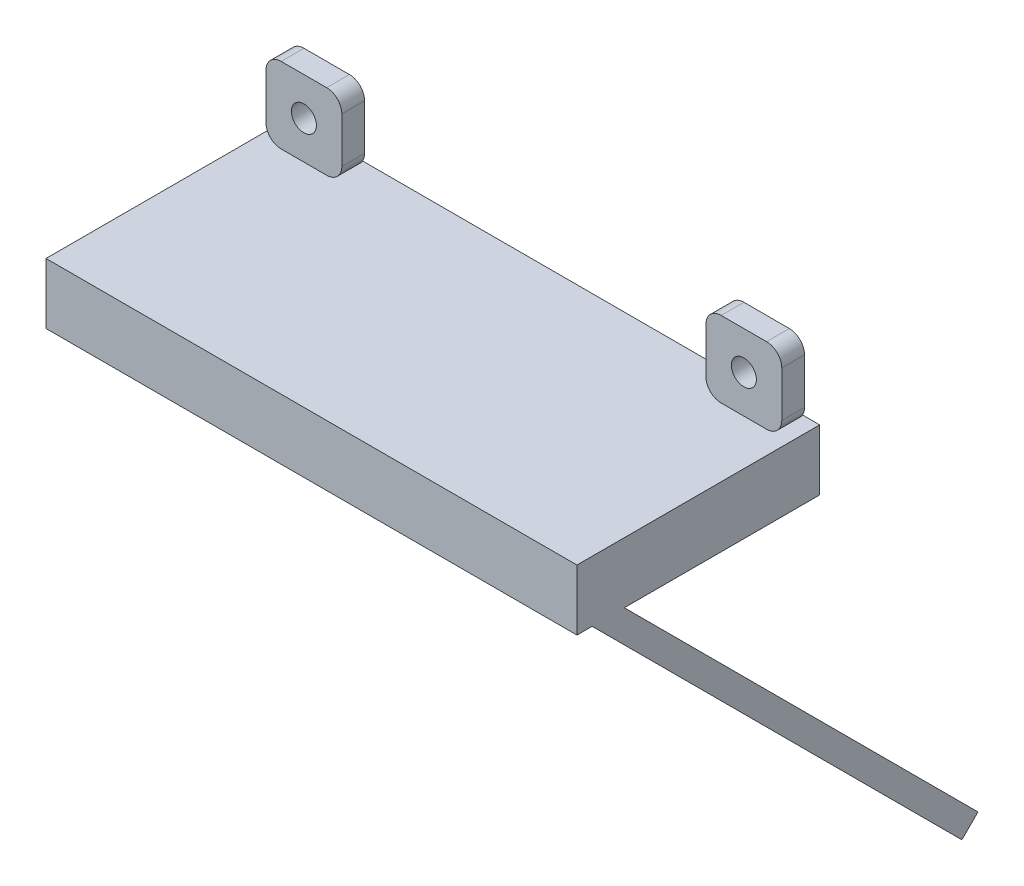
SolidWorks part; units mm, degrees
material "镁合金_CNC_暂定1800kg_m3"
ref_plane "前视基准面" through (0, 0, 0) normal (0, 0, 1) x (1, 0, 0)
ref_plane "上视基准面" through (0, 0, 0) normal (0, 1, 0) x (1, 0, 0)
ref_plane "右视基准面" through (0, 0, 0) normal (1, 0, 0) x (0, 0, -1)
other "Configuration Table"
sketch "草图1" plane through (0, 0, 0) normal (1, 0, 0) x (0, 0, -1)
  line L8 (16.7487, -84.7487) -> (-32.7487, -35.2513)
  line L9 (-32.7487, -35.2513) -> (-30.6274, -33.1299)
  line L10 (-30.6274, -33.1299) -> (18.8701, -82.6274)
  line L11 (18.8701, -82.6274) -> (16.7487, -84.7487)
extrude "70mm紧凑45度雷达承托面_3mm" add sketch "草图1" along normal blind 70 from offset 35
sketch "草图8" plane through (0, 0, 0) normal (0, 0, 1) x (1, 0, 0)
  line L0 (-35, -36) -> (35, -36)
  line L1 (35, -36) -> (35, -28)
  line L2 (35, -28) -> (-35, -28)
  line L3 (-35, -28) -> (-35, -36)
extrude "八毫米封闭后壁" add sketch "草图8" along normal blind 32 from offset 2
sketch "草图9" plane through (0, 0, 0) normal (0, 0, 1) x (1, 0, 0)
  line L0 (-32, -28) -> (-26, -28)
  line L1 (-24, -26) -> (-24, -20)
  line L2 (-26, -18) -> (-32, -18)
  line L3 (-34, -20) -> (-34, -26)
  arc A0 (-26, -28) -> (-24, -26) centre (-26, -26) ccw
  arc A1 (-24, -20) -> (-26, -18) centre (-26, -20) ccw
  arc A2 (-32, -18) -> (-34, -20) centre (-32, -20) ccw
  arc A3 (-34, -26) -> (-32, -28) centre (-32, -26) ccw
  circle A4 centre (-29, -23) radius 1.65
extrude "后M3安装脚_-1" add sketch "草图9" along normal blind 3 from offset 3
sketch "草图10" plane through (0, 0, 0) normal (0, 0, 1) x (1, 0, 0)
  line L0 (26, -28) -> (32, -28)
  line L1 (34, -26) -> (34, -20)
  line L2 (32, -18) -> (26, -18)
  line L3 (24, -20) -> (24, -26)
  arc A0 (32, -28) -> (34, -26) centre (32, -26) ccw
  arc A1 (34, -20) -> (32, -18) centre (32, -20) ccw
  arc A2 (26, -18) -> (24, -20) centre (26, -20) ccw
  arc A3 (24, -26) -> (26, -28) centre (26, -26) ccw
  circle A4 centre (29, -23) radius 1.65
extrude "后M3安装脚_1" add sketch "草图10" along normal blind 3 from offset 3
sketch "草图11" plane through (0, -34, 34) normal (0, -0.7071, 0.7071) x (1, 0, 0)
  circle A0 centre (-18, -60.7696) radius 1.65
  circle A1 centre (-18, -12.7696) radius 1.65
  circle A2 centre (18, -60.7696) radius 1.65
  circle A3 centre (18, -12.7696) radius 1.65
extrude "端口朝下雷达36x48四M3孔" cut sketch "草图11" along normal blind 3.1 and the other way blind 3.1
sketch "草图12" plane through (0, -34, 34) normal (0, -0.7071, 0.7071) x (1, 0, 0)
  circle A0 centre (-18, -12.7696) radius 3.2
  circle A1 centre (18, -12.7696) radius 3.2
extrude "后排雷达螺钉头盲孔避让" cut sketch "草图12" along normal blind 3.8 from offset 8
